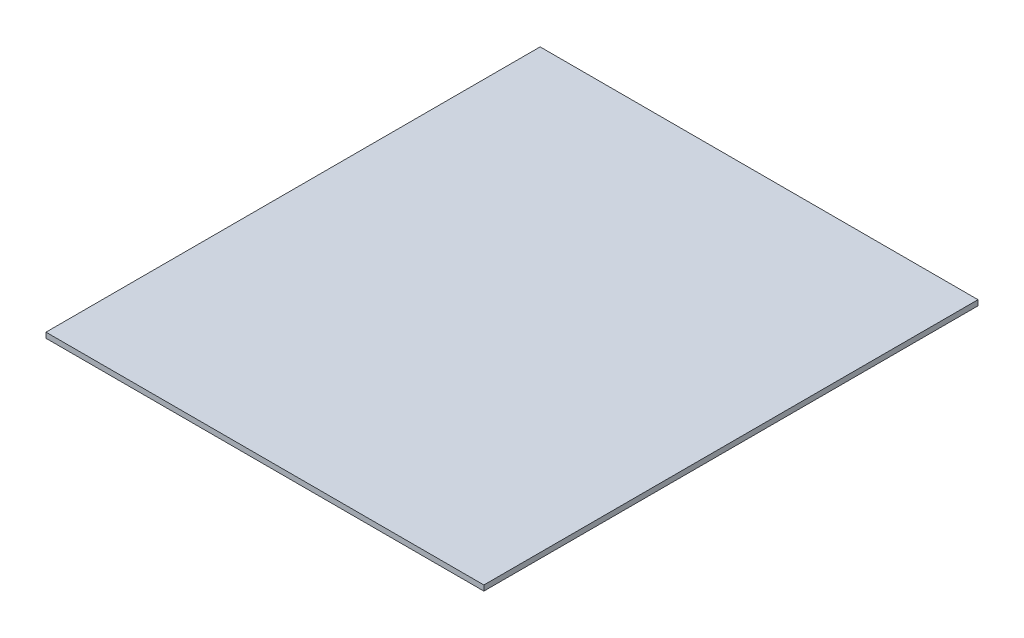
SolidWorks part; units mm, degrees
ref_plane "Front Plane" through (0, 0, 0) normal (0, 0, 1) x (1, 0, 0)
ref_plane "Top Plane" through (0, 0, 0) normal (0, 1, 0) x (1, 0, 0)
ref_plane "Right Plane" through (0, 0, 0) normal (1, 0, 0) x (0, 0, -1)
sketch "Sketch1" plane through (0, 0, 0) normal (0, 1, 0) x (1, 0, 0)
  line L1 (-259.5562, -292.8938) -> (259.5562, -292.8938)
  line L2 (-259.5562, -292.8938) -> (-259.5562, 292.8938)
  line L3 (-259.5562, 292.8938) -> (259.5562, 292.8938)
  line L4 (259.5562, -292.8938) -> (259.5562, 292.8938)
  line L5 (-259.5562, -292.8938) -> (259.5562, 292.8938) construction
  line L6 (-259.5562, 292.8938) -> (259.5562, -292.8938) construction
  point P0 (0, 0)
  dimension "D1" = 519.1125
  dimension "D2" = 585.7875
extrude "Boss-Extrude1" add sketch "Sketch1" along normal blind 6.35
